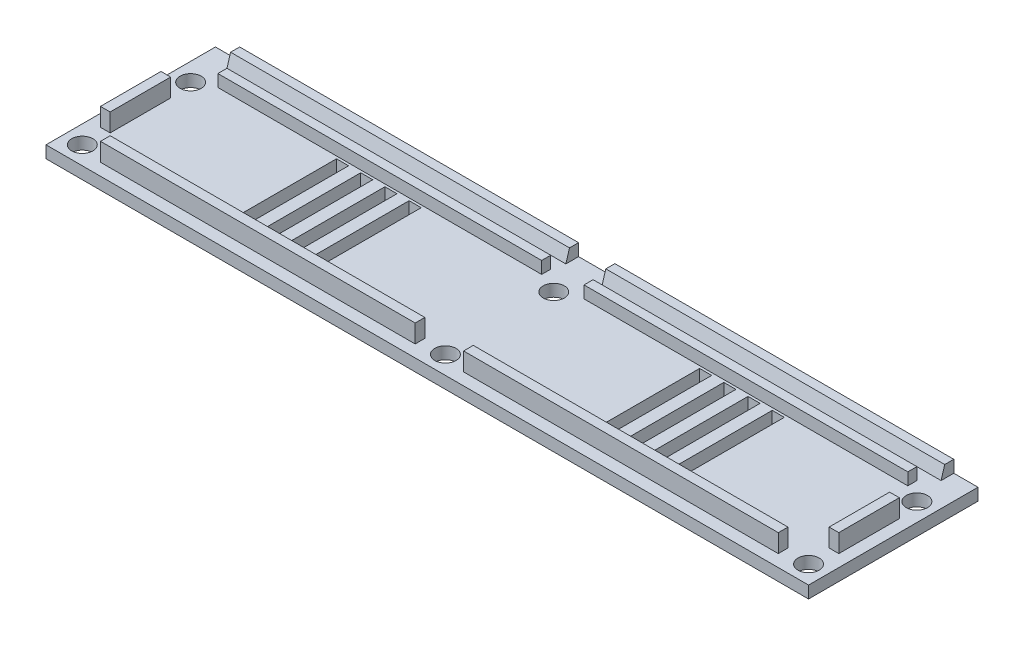
SolidWorks part; units mm, degrees
material "PET"
ref_plane "Ebene vorne" through (0, 0, 0) normal (0, 0, 1) x (1, 0, 0)
ref_plane "Ebene oben" through (0, 0, 0) normal (0, 1, 0) x (1, 0, 0)
ref_plane "Ebene rechts" through (0, 0, 0) normal (1, 0, 0) x (0, 0, -1)
sketch "Skizze1" plane through (0, 0, 0) normal (0, 1, 0) x (1, 0, 0)
  line L1 (0, 0) -> (126, 0)
  line L2 (0, 0) -> (0, 28)
  line L3 (0, 28) -> (126, 28)
  line L4 (126, 0) -> (126, 28)
  dimension "D1" = 28
  dimension "D2" = 126
extrude "Aufsatz-Linear austragen1" add sketch "Skizze1" along normal blind 2
sketch "Skizze2" plane through (0, 2, 0) normal (0, 1, 0) x (1, 0, 0)
  line L0 (0, 28) -> (0, 0) construction
  line L1 (0, 0) -> (126, 0) construction
  line L2 (126, 0) -> (126, 28) construction
  circle A0 centre (3, 3) radius 1.75
  circle A1 centre (3, 20.9) radius 1.75
  circle A2 centre (63, 3) radius 1.75
  circle A3 centre (63, 20.9) radius 1.75
  circle A4 centre (123, 20.9) radius 1.75
  circle A5 centre (123, 3) radius 1.75
  dimension "D1" = 3.5
  dimension "D2" = 3
  dimension "D3" = 3
  dimension "D4" = 3
  dimension "D5" = 3
  dimension "D6" = 17.9
  dimension "D7" = 60
extrude "Schnitt-Linear austragen1" cut sketch "Skizze2" against normal through all
sketch "Skizze3" plane through (0, 2, 0) normal (0, 1, 0) x (1, 0, 0)
  line L0 (0, 0) -> (126, 0) construction
  line L1 (26, 22) -> (28, 22)
  line L2 (26, 22) -> (26, 6)
  line L3 (26, 6) -> (28, 6)
  line L4 (28, 22) -> (28, 6)
  line L5 (0, 28) -> (0, 0) construction
  dimension "D1" = 2
  dimension "D2" = 16
  dimension "D3" = 6
  dimension "D4" = 26
extrude "Schnitt-Linear austragen2" cut sketch "Skizze3" against normal through all
pattern_linear "Lineares Muster1" count 4 spacing 4 along (1, 0, 0) of "Schnitt-Linear austragen2"
sketch "Skizze4" plane through (0, 2, 0) normal (0, 1, 0) x (1, 0, 0)
  line L0 (0, 0) -> (126, 0) construction
  line L1 (100, 22) -> (98, 22)
  line L2 (100, 22) -> (100, 6)
  line L3 (100, 6) -> (98, 6)
  line L4 (98, 22) -> (98, 6)
  line L5 (126, 0) -> (126, 28) construction
  dimension "D1" = 2
  dimension "D2" = 16
  dimension "D3" = 6
  dimension "D4" = 26
extrude "Schnitt-Linear austragen3" cut sketch "Skizze4" against normal through all
pattern_linear "Lineares Muster2" count 4 spacing 4 along (-1, 0, 0) of "Schnitt-Linear austragen3"
sketch "Skizze5" plane through (0, 2, 0) normal (0, 1, 0) x (1, 0, 0)
  line L0 (0, 0) -> (126, 0) construction
  line L1 (2, 17) -> (3.6, 17)
  line L2 (2, 17) -> (2, 7)
  line L3 (2, 7) -> (3.6, 7)
  line L4 (3.6, 17) -> (3.6, 7)
  line L5 (7, 3.6) -> (59, 3.6)
  line L6 (7, 3.6) -> (7, 2)
  line L7 (7, 2) -> (59, 2)
  line L8 (59, 3.6) -> (59, 2)
  line L9 (67, 3.6) -> (119, 3.6)
  line L10 (67, 3.6) -> (67, 2)
  line L11 (67, 2) -> (119, 2)
  line L12 (119, 3.6) -> (119, 2)
  line L13 (122.4, 17) -> (124, 17)
  line L14 (122.4, 17) -> (122.4, 7)
  line L15 (122.4, 7) -> (124, 7)
  line L16 (124, 17) -> (124, 7)
  line L17 (0, 28) -> (0, 0) construction
  line L18 (126, 0) -> (126, 28) construction
  dimension "D1" = 10
  dimension "D2" = 1.6
  dimension "D3" = 7
  dimension "D4" = 7
  dimension "D5" = 8
  dimension "D6" = 7
  dimension "D7" = 2
  dimension "D8" = 2
  dimension "D9" = 2
extrude "Aufsatz-Linear austragen2" add sketch "Skizze5" along normal blind 3
sketch "Skizze6" plane through (0, 2, 0) normal (0, 1, 0) x (1, 0, 0)
  line L0 (0, 28) -> (0, 0) construction
  line L1 (6, 22.4) -> (59.5, 22.4)
  line L2 (6, 22.4) -> (6, 23.9)
  line L3 (6, 23.9) -> (59.5, 23.9)
  line L4 (59.5, 22.4) -> (59.5, 23.9)
  line L5 (66.5, 22.4) -> (120, 22.4)
  line L6 (66.5, 22.4) -> (66.5, 23.9)
  line L7 (66.5, 23.9) -> (120, 23.9)
  line L8 (120, 22.4) -> (120, 23.9)
  line L9 (126, 0) -> (126, 28) construction
  line L10 (126, 28) -> (0, 28) construction
  dimension "D1" = 53.5
  dimension "D2" = 1.5
  dimension "D3" = 6
  dimension "D4" = 6
  dimension "D5" = 4.1
extrude "Aufsatz-Linear austragen3" add sketch "Skizze6" along normal blind 2
sketch "Skizze7" plane through (0, 2, 0) normal (0, 1, 0) x (1, 0, 0)
  line L0 (126, 28) -> (0, 28) construction
  line L1 (4, 28) -> (60, 28)
  line L2 (4, 28) -> (4, 25.9)
  line L3 (4, 25.9) -> (60, 25.9)
  line L4 (60, 28) -> (60, 25.9)
  line L5 (0, 28) -> (0, 0) construction
  line L6 (66, 28) -> (122, 28)
  line L7 (66, 28) -> (66, 25.9)
  line L8 (66, 25.9) -> (122, 25.9)
  line L9 (122, 28) -> (122, 25.9)
  line L10 (126, 0) -> (126, 28) construction
  dimension "D1" = 2.1
  dimension "D2" = 56
  dimension "D3" = 4
  dimension "D4" = 4
extrude "Aufsatz-Linear austragen4" add sketch "Skizze7" along normal blind 2
chamfer "Fase1" distance 2 distance2 0.6 2 edges at (94, 4, -25.9) (32, 4, -25.9) first distance on face at (94, 3, -25.9) first distance on face at (32, 3, -25.9)
